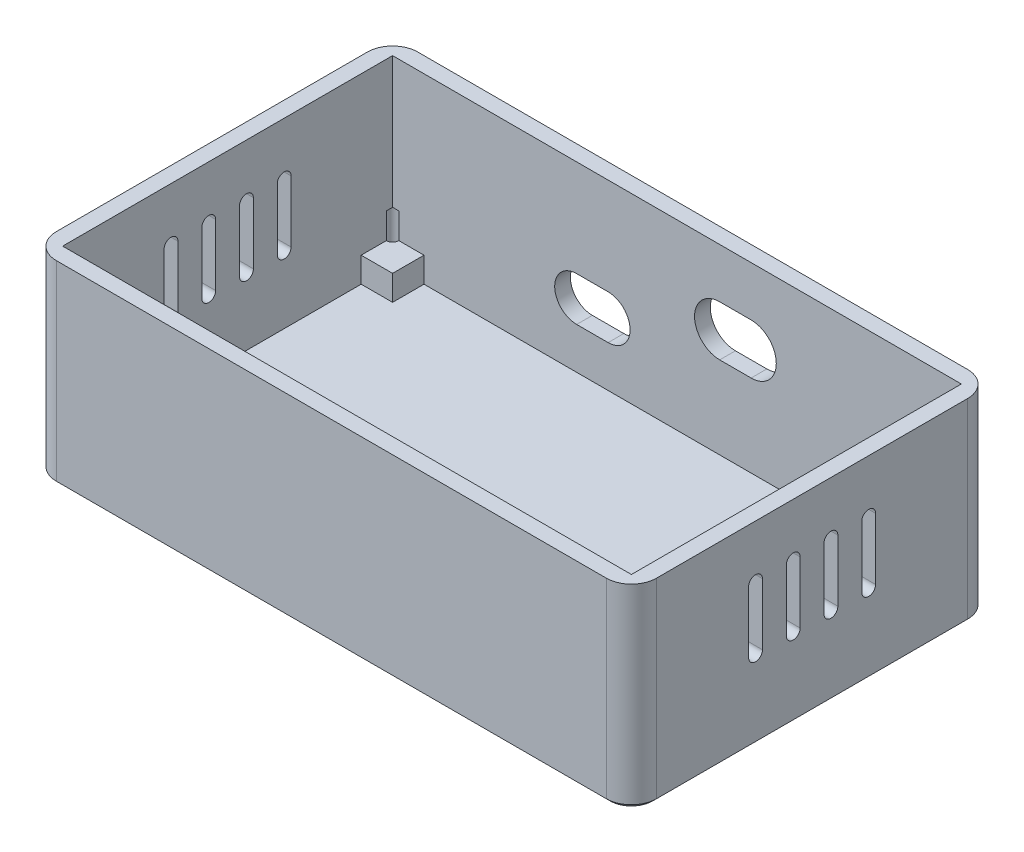
SolidWorks part; units mm, degrees
ref_plane "Front Plane" through (0, 0, 0) normal (0, 0, 1) x (1, 0, 0)
ref_plane "Top Plane" through (0, 0, 0) normal (0, 1, 0) x (1, 0, 0)
ref_plane "Right Plane" through (0, 0, 0) normal (1, 0, 0) x (0, 0, -1)
sketch "Croquis_contorno" plane through (0, 0, 0) normal (0, 1, 0) x (1, 0, 0)
  line L0 (-43.75, -28.75) -> (43.75, -28.75)
  line L1 (47.75, -24.75) -> (47.75, 24.75)
  line L2 (43.75, 28.75) -> (-43.75, 28.75)
  line L3 (-47.75, 24.75) -> (-47.75, -24.75)
  arc A0 (43.75, -28.75) -> (47.75, -24.75) centre (43.75, -24.75) ccw
  arc A1 (47.75, 24.75) -> (43.75, 28.75) centre (43.75, 24.75) ccw
  arc A2 (-43.75, 28.75) -> (-47.75, 24.75) centre (-43.75, 24.75) ccw
  arc A3 (-47.75, -24.75) -> (-43.75, -28.75) centre (-43.75, -24.75) ccw
  dimension "D3" = 4
  dimension "D1" = 95.5
  dimension "D2" = 57.5
extrude "Cuerpo" add sketch "Croquis_contorno" along normal blind 31
ref_plane "Plano_Top Plane_+31" through (0, 31, 0) normal (0, 1, 0) x (1, 0, 0)
sketch "Croquis_hueco_PCB" plane through (0, 31, 0) normal (0, 1, 0) x (1, 0, 0)
  line L1 (-45.25, -26.25) -> (45.25, -26.25)
  line L2 (-45.25, -26.25) -> (-45.25, 26.25)
  line L3 (-45.25, 26.25) -> (45.25, 26.25)
  line L4 (45.25, -26.25) -> (45.25, 26.25)
  line L5 (-45.25, -26.25) -> (45.25, 26.25) construction
  line L6 (-45.25, 26.25) -> (45.25, -26.25) construction
  dimension "D1" = 90.5
  dimension "D2" = 52.5
extrude "Hueco_PCB" cut sketch "Croquis_hueco_PCB" against normal blind 29
ref_plane "Plano_Top Plane_+2" through (0, 2, 0) normal (0, 1, 0) x (1, 0, 0)
sketch "Croquis_apoyos" plane through (0, 2, 0) normal (0, 1, 0) x (1, 0, 0)
  line L0 (45.25, 26.25) -> (-45.25, 26.25) construction
  line L1 (-45.25, -26.25) -> (-40.25, -26.25)
  line L2 (-45.25, -26.25) -> (-45.25, -21.25)
  line L3 (-45.25, -21.25) -> (-40.25, -21.25)
  line L4 (-40.25, -26.25) -> (-40.25, -21.25)
  line L5 (-45.25, -26.25) -> (-40.25, -21.25) construction
  line L6 (-45.25, -21.25) -> (-40.25, -26.25) construction
  line L7 (-45.25, 21.25) -> (-40.25, 21.25)
  line L8 (-45.25, 21.25) -> (-45.25, 26.25)
  line L9 (-45.25, 26.25) -> (-40.25, 26.25)
  line L10 (-40.25, 21.25) -> (-40.25, 26.25)
  line L11 (-45.25, 21.25) -> (-40.25, 26.25) construction
  line L12 (-45.25, 26.25) -> (-40.25, 21.25) construction
  line L13 (45.25, -26.25) -> (45.25, 26.25) construction
  line L14 (40.25, -26.25) -> (45.25, -26.25)
  line L15 (40.25, -26.25) -> (40.25, -21.25)
  line L16 (40.25, -21.25) -> (45.25, -21.25)
  line L17 (45.25, -26.25) -> (45.25, -21.25)
  line L18 (40.25, -26.25) -> (45.25, -21.25) construction
  line L19 (40.25, -21.25) -> (45.25, -26.25) construction
  line L21 (40.25, 21.25) -> (45.25, 21.25)
  line L22 (40.25, 21.25) -> (40.25, 26.25)
  line L23 (40.25, 26.25) -> (45.25, 26.25)
  line L24 (45.25, 21.25) -> (45.25, 26.25)
  line L25 (40.25, 21.25) -> (45.25, 26.25) construction
  line L26 (40.25, 26.25) -> (45.25, 21.25) construction
  point P0 (-42.75, 23.75)
  point P11 (42.75, -23.75)
  point P18 (42.75, 23.75)
  dimension "D1" = 5
  dimension "D2" = 5
extrude "Apoyos_PCB" add sketch "Croquis_apoyos" along normal blind 4
sketch "Croquis_alivios" plane through (0, 2, 0) normal (0, 1, 0) x (1, 0, 0)
  circle A0 centre (-45.25, -26.25) radius 1
  circle A1 centre (-45.25, 26.25) radius 1
  circle A2 centre (45.25, -26.25) radius 1
  circle A3 centre (45.25, 26.25) radius 1
  dimension "D1" = 2
extrude "Alivios_esquinas" cut sketch "Croquis_alivios" along normal blind 8.1
sketch "Croquis_salidas" plane through (0, 0, 0) normal (0, 0, 1) x (1, 0, 0)
  line L0 (6.8, 19.1) -> (11.8, 19.1) construction
  line L1 (6.8, 23.1) -> (11.8, 23.1)
  line L2 (6.8, 15.1) -> (11.8, 15.1)
  line L3 (-15.96, 12.1) -> (-10.96, 12.1) construction
  line L4 (-15.96, 15.6) -> (-10.96, 15.6)
  line L5 (-15.96, 8.6) -> (-10.96, 8.6)
  arc A0 (6.8, 23.1) -> (6.8, 15.1) centre (6.8, 19.1) ccw
  arc A1 (11.8, 15.1) -> (11.8, 23.1) centre (11.8, 19.1) ccw
  arc A2 (-15.96, 15.6) -> (-15.96, 8.6) centre (-15.96, 12.1) ccw
  arc A3 (-10.96, 8.6) -> (-10.96, 15.6) centre (-10.96, 12.1) ccw
  point P2 (9.3, 19.1)
  point P7 (-13.46, 12.1)
  point P14 (0, 0)
extrude "Salidas_USB_y_panel" cut sketch "Croquis_salidas" against normal through all
sketch "Croquis_ventilas" plane through (0, 0, 0) normal (1, 0, 0) x (0, 0, -1)
  line L0 (-9, 12.7) -> (-9, 22.5) construction
  line L1 (-10.1, 12.7) -> (-10.1, 22.5)
  line L2 (-7.9, 12.7) -> (-7.9, 22.5)
  line L3 (-3, 12.7) -> (-3, 22.5) construction
  line L4 (-4.1, 12.7) -> (-4.1, 22.5)
  line L5 (-1.9, 12.7) -> (-1.9, 22.5)
  line L6 (3, 12.7) -> (3, 22.5) construction
  line L7 (1.9, 12.7) -> (1.9, 22.5)
  line L8 (4.1, 12.7) -> (4.1, 22.5)
  line L9 (9, 12.7) -> (9, 22.5) construction
  line L10 (7.9, 12.7) -> (7.9, 22.5)
  line L11 (10.1, 12.7) -> (10.1, 22.5)
  arc A0 (-10.1, 12.7) -> (-7.9, 12.7) centre (-9, 12.7) ccw
  arc A1 (-7.9, 22.5) -> (-10.1, 22.5) centre (-9, 22.5) ccw
  arc A2 (-4.1, 12.7) -> (-1.9, 12.7) centre (-3, 12.7) ccw
  arc A3 (-1.9, 22.5) -> (-4.1, 22.5) centre (-3, 22.5) ccw
  arc A4 (1.9, 12.7) -> (4.1, 12.7) centre (3, 12.7) ccw
  arc A5 (4.1, 22.5) -> (1.9, 22.5) centre (3, 22.5) ccw
  arc A6 (7.9, 12.7) -> (10.1, 12.7) centre (9, 12.7) ccw
  arc A7 (10.1, 22.5) -> (7.9, 22.5) centre (9, 22.5) ccw
  point P2 (-9, 17.6)
  point P7 (-3, 17.6)
  point P14 (3, 17.6)
  point P21 (9, 17.6)
  point P28 (0, 0)
extrude "Ventilas_laterales" cut sketch "Croquis_ventilas" along normal through all and the other way through all
chamfer "Chaflan_base" distance 0.6 angle 45 8 edges at (0, 0, 28.75) (46.5784, 0, 27.5784) (47.75, 0, 0) (46.5784, 0, -27.5784) (0, 0, -28.75) (-46.5784, 0, -27.5784) (-47.75, 0, 0) (-46.5784, 0, 27.5784) tangent propagation no
